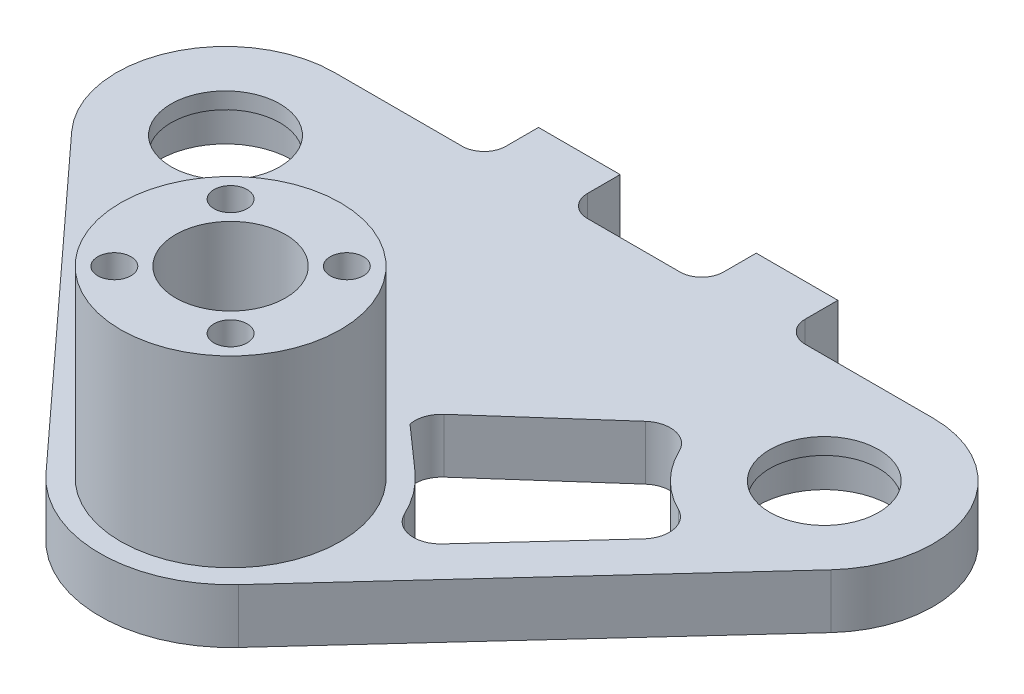
SolidWorks part; units mm, degrees
material "PLA Infill"
ref_plane "Front Plane" through (0, 0, 0) normal (0, 0, 1) x (1, 0, 0)
ref_plane "Top Plane" through (0, 0, 0) normal (0, 1, 0) x (1, 0, 0)
ref_plane "Right Plane" through (0, 0, 0) normal (1, 0, 0) x (0, 0, -1)
sketch "Sketch1" plane through (0, 0, 0) normal (0, 1, 0) x (1, 0, 0)
  line L0 (0, 0) -> (55, 54.0672) construction
  line L1 (55, 54.0672) -> (-55, 54.0672) construction
  line L2 (-55, 54.0672) -> (0, 0) construction
  line L3 (-69.7415, 40.551) -> (-17.6898, -16.2194)
  line L4 (-41.7379, 69.0378) -> (15.9145, 17.9646)
  line L5 (-47.6255, 28.2677) -> (-29.9271, 8.9649)
  line L6 (-29.0781, 47.135) -> (-9.4754, 29.7694)
  circle A0 centre (0, 0) radius 10.1
  circle A1 centre (-55, 54.0672) radius 10
  circle A2 centre (0, 0) radius 24 construction
  circle A3 centre (-55, 54.0672) radius 20 construction
  arc A4 (-69.7415, 40.551) -> (-41.7379, 69.0378) centre (-55, 54.0672) cw
  arc A5 (-17.6898, -16.2194) -> (15.9145, 17.9646) centre (0, 0) ccw
  arc A6 (-46.1521, 36.1308) -> (-36.9149, 45.5274) centre (-55, 54.0672) ccw
  arc A7 (-21.7173, 10.2157) -> (-10.5856, 21.5394) centre (0, 0) cw
  arc A8 (-29.9271, 8.9649) -> (-21.7173, 10.2157) centre (-26.2417, 12.3439) ccw
  arc A9 (-9.4754, 29.7694) -> (-10.5856, 21.5394) centre (-12.7909, 26.0268) cw
  arc A10 (-29.0781, 47.135) -> (-36.9149, 45.5274) centre (-32.3936, 43.3924) ccw
  arc A11 (-47.6255, 28.2677) -> (-46.1521, 36.1308) centre (-43.9401, 31.6467) cw
  point P22 (-23.8825, 2.3723)
  point P25 (-2.7804, 23.8384)
  point P28 (-35.0663, 52.4399)
  point P31 (-53.032, 34.1643)
  dimension "D3" = 20.2
  dimension "D4" = 20
  dimension "D5" = 48
  dimension "D6" = 40
  dimension "D9" = 5
  dimension "D1" = 77.125
  dimension "D2" = 110
  dimension "D7" = 8
  dimension "D8" = 8
extrude "Main Body" add sketch "Sketch1" along normal blind 10
sketch "Sketch2" plane through (0, 0, 0) normal (0, -1, 0) x (1, 0, 0)
  circle A0 centre (-55, -54.0672) radius 10 construction
  circle A1 centre (-55, -54.0672) radius 10 construction
  circle A2 centre (-55, -54.0672) radius 12.2
  dimension "D1" = 24.4
extrude "Bearing Recess" cut sketch "Sketch2" against normal blind 7
sketch "Sketch3" plane through (0, 0, 0) normal (0, -1, 0) x (1, 0, 0)
  circle A0 centre (0, 0) radius 21.5
  circle A1 centre (0, 0) radius 10.1
  circle A2 centre (0, 0) radius 10.1 construction
  dimension "D1" = 43
extrude "Standoff Section" add sketch "Sketch3" along normal blind 1.5
sketch "Sketch9" plane through (0, 10, 0) normal (0, 1, 0) x (1, 0, 0)
  circle A0 centre (0, 0) radius 20.2
  circle A1 centre (0, 0) radius 10.1
  dimension "D1" = 40.4
  dimension "D2" = 20.2
extrude "Boss-Extrude1" add sketch "Sketch9" along normal blind 33.7
ref_plane "Mirror Plane" through (0, 0, 0) normal (1, 0, 0) x (0, 0, -1)
sketch "Sketch6" plane through (0, 0, 0) normal (0, 1, 0) x (1, 0, 0)
  line L0 (-55, 74.0672) -> (0, 74.0672) construction
  line L1 (0, -24.86) -> (0, 24.86) construction
  line L2 (0, 74.0672) -> (0, 32.063)
  line L3 (-41.7379, 69.0378) -> (15.9145, 17.9646) construction
  line L4 (0, 32.063) -> (-41.7379, 69.0378)
  line L5 (-20, 84.0672) -> (-20, 74.0672) construction
  line L6 (-27.5, 74.0672) -> (-12.5, 74.0672) construction
  line L7 (-27.5, 78.0672) -> (-27.5, 84.0672)
  line L8 (-27.5, 84.0672) -> (-12.5, 84.0672)
  line L9 (-12.5, 78.0672) -> (-12.5, 84.0672)
  line L10 (-55, 74.0672) -> (-31.5, 74.0672)
  line L11 (-8.5, 74.0672) -> (0, 74.0672)
  arc A0 (-41.7379, 69.0378) -> (-69.7415, 40.551) centre (-55, 54.0672) ccw construction
  arc A1 (-41.7379, 69.0378) -> (-69.7415, 40.551) centre (-55, 54.0672) ccw construction
  arc A2 (-55, 74.0672) -> (-41.7379, 69.0378) centre (-55, 54.0672) cw
  arc A3 (-8.5, 74.0672) -> (-12.5, 78.0672) centre (-8.5, 78.0672) cw
  arc A4 (-31.5, 74.0672) -> (-27.5, 78.0672) centre (-31.5, 78.0672) ccw
  dimension "D4" = 4
  dimension "D1" = 10
  dimension "D2" = 20
  dimension "D3" = 15
extrude "Extra Geometry" add sketch "Sketch6" along normal blind 10
sketch "Sketch8" plane through (0, 0, -84.0672) normal (0, 0, -1) x (-1, 0, 0)
  line L0 (20, 10) -> (20, 0) construction
  line L1 (12.5, 10) -> (27.5, 10) construction
  line L2 (12.5, 0) -> (27.5, 0) construction
  circle A0 centre (20, 5) radius 2
  point P9 (20, 5)
  dimension "D1" = 4
extrude "Cut-Extrude1" cut sketch "Sketch8" against normal blind 6
mirror "Mirror2" about plane through (0, 0, 0) normal (1, 0, 0) of bodies 109 107
sketch "Sketch4" plane through (0, -1.5, 0) normal (0, -1, 0) x (1, 0, 0)
  line L0 (0, 0) -> (50000, 0) construction
  line L1 (55, -54.0672) -> (-55, -54.0672) construction
  line L2 (-10.6773, 10.6773) -> (0, 0) construction
  circle A0 centre (-10.6773, 10.6773) radius 3.05
  circle A2 centre (10.6773, 10.6773) radius 3.05
  circle A3 centre (10.6773, -10.6773) radius 3.05
  circle A4 centre (-10.6773, -10.6773) radius 3.05
  dimension "D1" = 6.1
  dimension "D2" = 15.1
  dimension "D3" = 45
  dimension "D4" = 4
extrude "M6 Bolt holes" cut sketch "Sketch4" against normal through all
